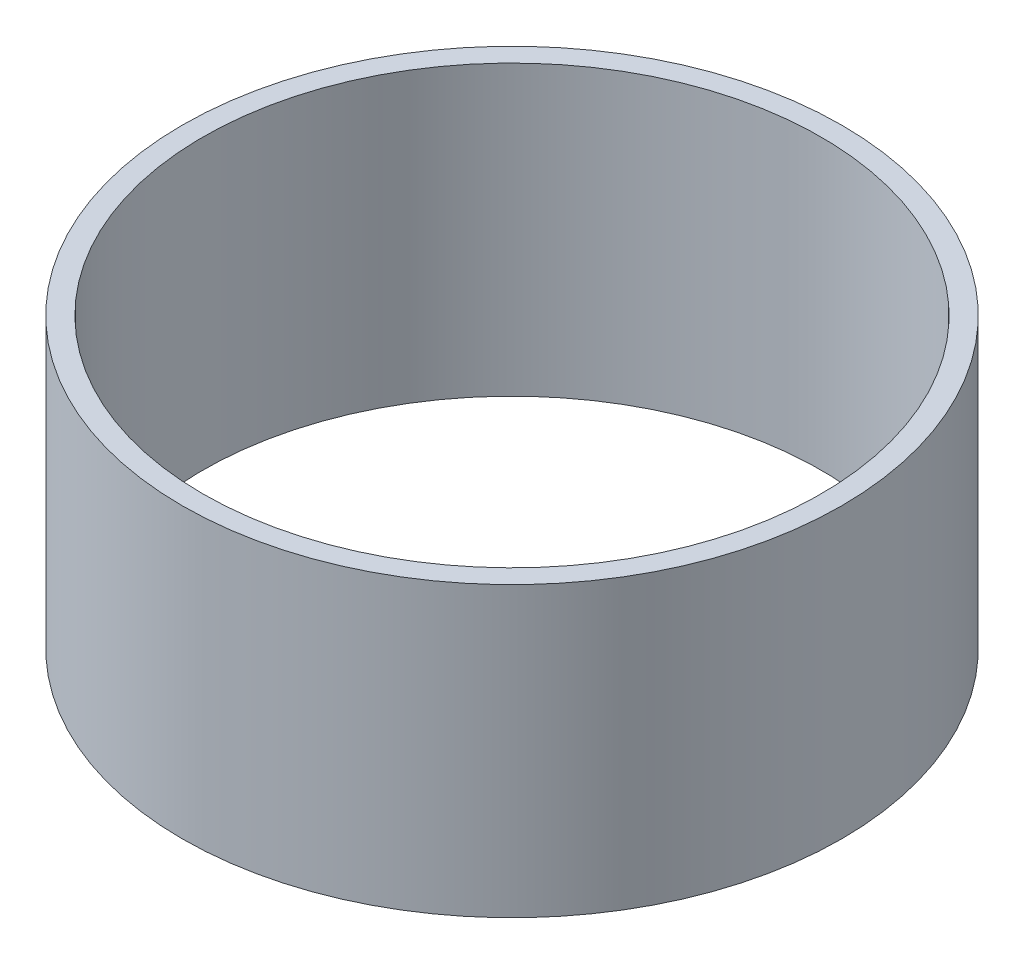
SolidWorks part; units mm, degrees
ref_plane "Front Plane" through (0, 0, 0) normal (0, 0, 1) x (1, 0, 0)
ref_plane "Top Plane" through (0, 0, 0) normal (0, 1, 0) x (1, 0, 0)
ref_plane "Right Plane" through (0, 0, 0) normal (1, 0, 0) x (0, 0, -1)
sketch "Sketch1" plane through (0, 0, 0) normal (0, 1, 0) x (1, 0, 0)
  circle A0 centre (0, 0) radius 30
  dimension "D1" = 60
extrude "Extrude-Thin1" add sketch "Sketch1" along normal blind 28 thin thin type one direction wall 2
